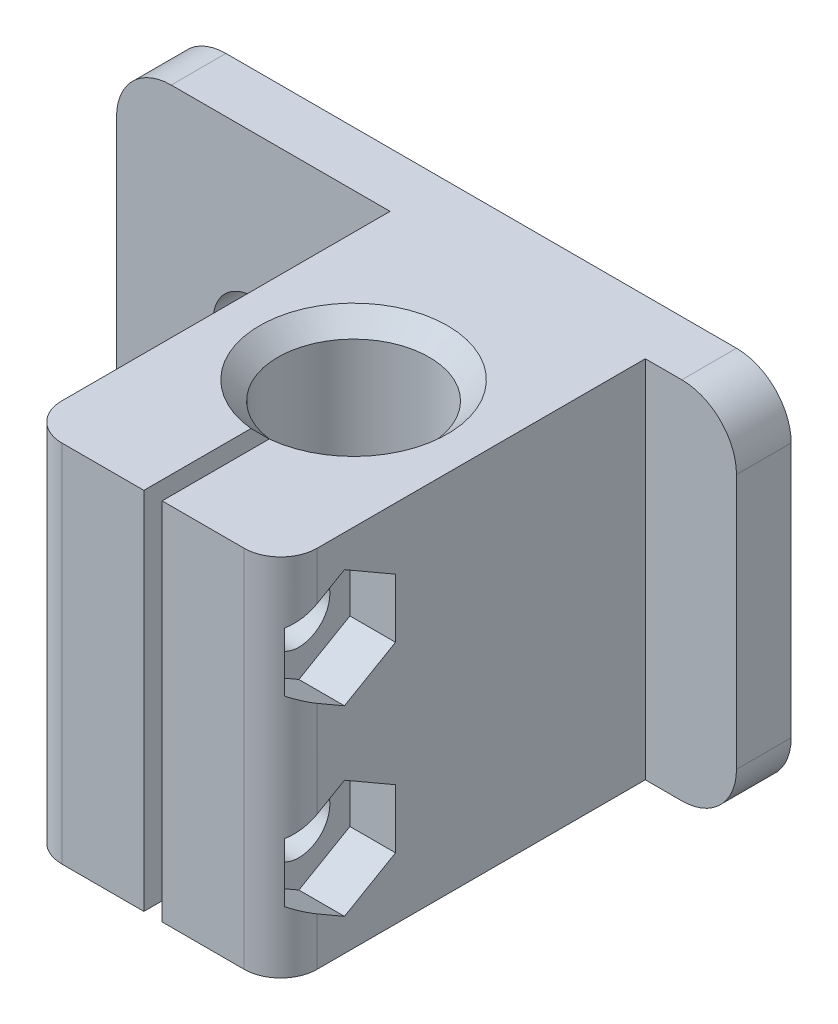
SolidWorks part; units mm, degrees
material "ABS"
ref_plane "Front Plane" through (0, 0, 0) normal (0, 0, 1) x (1, 0, 0)
ref_plane "Top Plane" through (0, 0, 0) normal (0, 1, 0) x (1, 0, 0)
ref_plane "Right Plane" through (0, 0, 0) normal (1, 0, 0) x (0, 0, -1)
sketch "Sketch1" plane through (0, 0, 0) normal (0, 0, 1) x (1, 0, 0)
  line L1 (-17, -10) -> (17, -10)
  line L2 (-17, -10) -> (-17, 10)
  line L3 (-17, 10) -> (17, 10)
  line L4 (17, -10) -> (17, 10)
  line L5 (-17, -10) -> (17, 10) construction
  line L6 (-17, 10) -> (17, -10) construction
  point P0 (0, 0)
  dimension "D1" = 20
  dimension "D2" = 34
extrude "Boss-Extrude1" add sketch "Sketch1" along normal blind 3
fillet "Fillet1" radius 3 4 edges at (17, -10, 1.5) (-17, -10, 1.5) (-17, 10, 1.5) (17, 10, 1.5)
sketch "Sketch2" plane through (0, 0, 3) normal (0, 0, 1) x (1, 0, 0)
  line L0 (14, 10) -> (-14, 10) construction
  line L1 (12, 10) -> (-2, 10)
  line L2 (12, 10) -> (12, -10)
  line L3 (12, -10) -> (-2, -10)
  line L4 (-2, 10) -> (-2, -10)
  line L5 (-14, -10) -> (14, -10) construction
  line L6 (17, -7) -> (17, 7) construction
  dimension "D1" = 14
  dimension "D2" = 5
extrude "Boss-Extrude2" add sketch "Sketch2" along normal blind 20
sketch "Sketch3" plane through (0, 10, 0) normal (0, 1, 0) x (1, 0, 0)
  line L0 (5, -12) -> (5, -23) construction
  line L1 (12, -23) -> (-2, -23) construction
  line L2 (4.5, -16.1198) -> (4.5, -23)
  line L3 (5.5, -16.1198) -> (5.5, -23)
  line L4 (4.5, -23) -> (5.5, -23)
  line L5 (14, 0) -> (-14, 0) construction
  arc A0 (5.5, -16.1198) -> (4.5, -16.1198) centre (5, -12) ccw
  dimension "D1" = 8.3
  dimension "D2" = 12
  dimension "D3" = 1
extrude "Cut-Extrude1" cut sketch "Sketch3" against normal through all
chamfer "Chamfer1" distance 1 angle 45 2 edges at (5, -10, 7.85) (5, 10, 7.85)
sketch "Sketch4" plane through (0, 0, 3) normal (0, 0, 1) x (1, 0, 0)
  line L0 (-2, 10) -> (-14, 10) construction
  line L1 (-17, 7) -> (-17, -7) construction
  circle A0 centre (-9.5, 0) radius 2.2
  point P4 (-8, 10)
  dimension "D1" = 4.4
  dimension "D2" = 10
  dimension "D3" = 7.5
extrude "Cut-Extrude2" cut sketch "Sketch4" against normal through all
sketch "Sketch5" plane through (12, 0, 0) normal (1, 0, 0) x (0, 0, -1)
  line L0 (0, -7) -> (0, 7) construction
  line L1 (-19.5, 5) -> (-19.5, -5) construction
  line L2 (-19.5, 0) -> (-23, 0) construction
  line L3 (-23, -10) -> (-23, 10) construction
  circle A0 centre (-19.5, 5) radius 1.7
  circle A1 centre (-19.5, -5) radius 1.7
  dimension "D1" = 3.4
  dimension "D2" = 10
  dimension "D3" = 19.5
extrude "Cut-Extrude3" cut sketch "Sketch5" against normal through all
fillet "Fillet2" radius 2 2 edges at (-2, 0, 23) (12, 0, 23)
sketch "Sketch6" plane through (12, 0, 0) normal (1, 0, 0) x (0, 0, -1)
  line L1 (-16.7, 3.3834) -> (-16.7, 6.6166)
  line L2 (-16.7, 6.6166) -> (-19.5, 8.2332)
  line L3 (-19.5, 8.2332) -> (-22.3, 6.6166)
  line L4 (-22.3, 6.6166) -> (-22.3, 3.3834)
  line L5 (-22.3, 3.3834) -> (-19.5, 1.7668)
  line L6 (-19.5, 1.7668) -> (-16.7, 3.3834)
  line L7 (-16.7, -3.3834) -> (-19.5, -1.7668)
  line L8 (-19.5, -1.7668) -> (-22.3, -3.3834)
  line L9 (-22.3, -3.3834) -> (-22.3, -6.6166)
  line L10 (-22.3, -6.6166) -> (-19.5, -8.2332)
  line L11 (-19.5, -8.2332) -> (-16.7, -6.6166)
  line L12 (-16.7, -6.6166) -> (-16.7, -3.3834)
  circle A0 centre (-19.5, 5) radius 2.8 construction
  circle A1 centre (-19.5, -5) radius 2.8 construction
  dimension "D1" = 5.6
extrude "Cut-Extrude4" cut sketch "Sketch6" against normal blind 2.5
sketch "Sketch7" plane through (-2, 0, 0) normal (-1, 0, 0) x (0, 0, 1)
  circle A0 centre (19.5, 5) radius 2.75
  circle A1 centre (19.5, -5) radius 2.75
  dimension "D1" = 5.5
extrude "Cut-Extrude5" cut sketch "Sketch7" against normal blind 3
